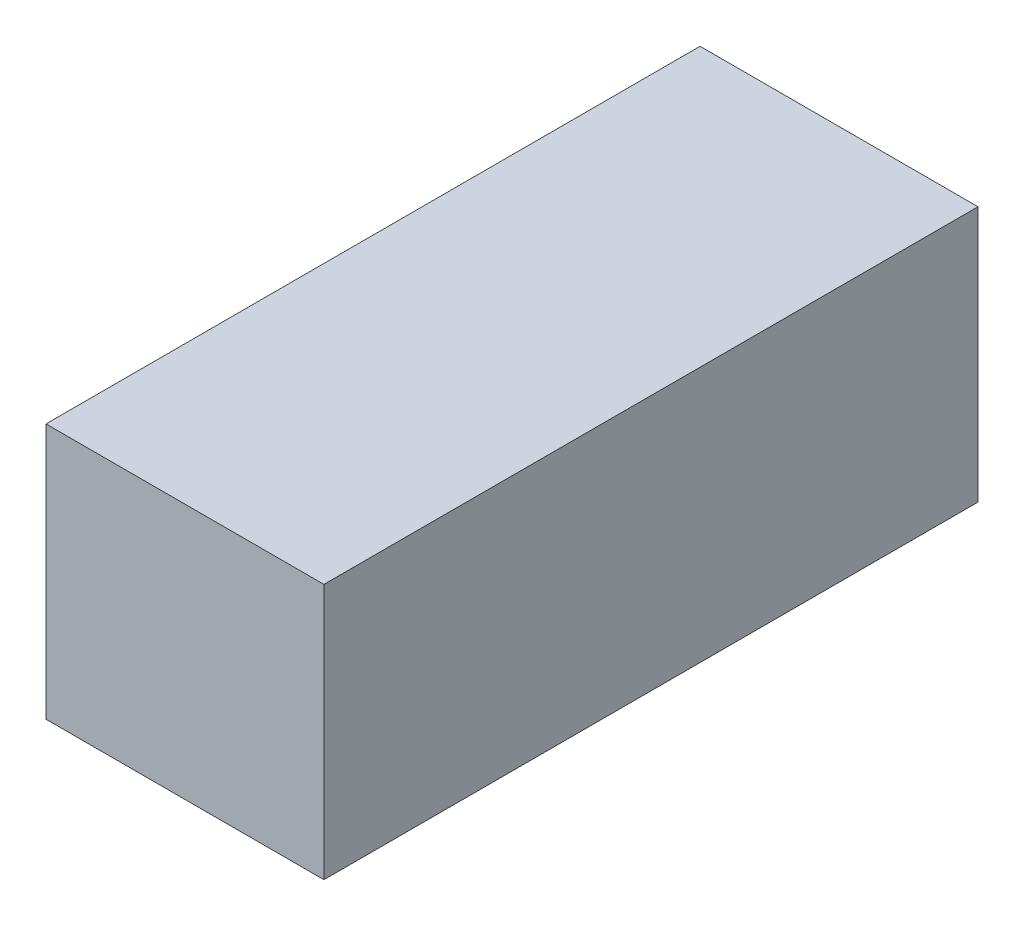
SolidWorks part; units mm, degrees
ref_plane "Piano frontale" through (0, 0, 0) normal (0, 0, 1) x (1, 0, 0)
ref_plane "Piano superiore" through (0, 0, 0) normal (0, 1, 0) x (1, 0, 0)
ref_plane "Piano destro" through (0, 0, 0) normal (1, 0, 0) x (0, 0, -1)
sketch "Schizzo1" plane through (0, 0, 0) normal (0, 0, 1) x (1, 0, 0)
  line L1 (-175.5, -161.5) -> (175.5, -161.5)
  line L2 (-175.5, -161.5) -> (-175.5, 161.5)
  line L3 (-175.5, 161.5) -> (175.5, 161.5)
  line L4 (175.5, -161.5) -> (175.5, 161.5)
  line L5 (-175.5, -161.5) -> (175.5, 161.5) construction
  line L6 (-175.5, 161.5) -> (175.5, -161.5) construction
  point P0 (0, 0)
  dimension "D1" = 351
  dimension "D2" = 323
extrude "Estrusione-Estrusione1" add sketch "Schizzo1" along normal blind 413 and the other way blind 413
